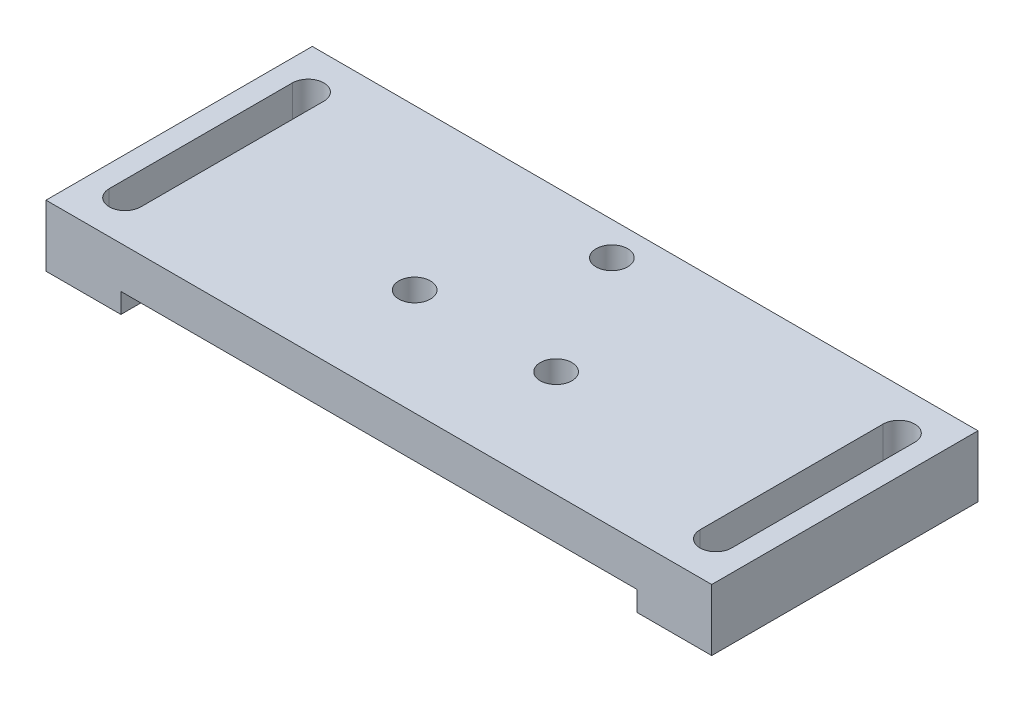
SolidWorks part; units mm, degrees
ref_plane "Front Plane" through (0, 0, 0) normal (0, 0, 1) x (1, 0, 0)
ref_plane "Top Plane" through (0, 0, 0) normal (0, 1, 0) x (1, 0, 0)
ref_plane "Right Plane" through (0, 0, 0) normal (1, 0, 0) x (0, 0, -1)
ref_axis "X-Axis" through (-88.99, 0, 0) along (1, 0, 0)
ref_axis "Y-Axis" through (0, 55, 0) along (0, -1, 0)
ref_axis "Z-Axis" through (0, 0, -88.99) along (0, 0, 1)
sketch "Sketch1" plane through (0, 0, 0) normal (0, 1, 0) x (1, 0, 0)
  line L1 (-20, -8) -> (20, -8)
  line L2 (-20, -8) -> (-20, 8)
  line L3 (-20, 8) -> (20, 8)
  line L4 (20, -8) -> (20, 8)
  line L5 (-20, -8) -> (20, 8) construction
  line L6 (-20, 8) -> (20, -8) construction
  point P0 (0, 0)
  dimension "D1" = 40
  dimension "D2" = 16
extrude "Boss-Extrude1" add sketch "Sketch1" along normal blind 2.5
sketch "Sketch2" plane through (0, 0, 0) normal (0, -1, 0) x (1, 0, 0)
  line L0 (20, -8) -> (-20, -8) construction
  line L1 (-20, 8) -> (-15.5, 8)
  line L2 (-20, 8) -> (-20, -8)
  line L3 (-20, -8) -> (-15.5, -8)
  line L4 (-15.5, 8) -> (-15.5, -8)
  dimension "D1" = 4.5
extrude "Boss-Extrude2" add sketch "Sketch2" along normal offset from surface (1.2 mm away) 3.7 up to face at (0, 2.5, 0)
sketch "Sketch3" plane through (0, -1.2, 0) normal (0, -1, 0) x (1, 0, 0)
  line L0 (-17.75, 8) -> (-17.75, -8) construction
  line L1 (-15.5, 8) -> (-20, 8) construction
  line L2 (-20, -8) -> (-15.5, -8) construction
  line L3 (-17.75, 5.5) -> (-17.75, -5.5) construction
  line L4 (-16.8, 5.5) -> (-16.8, -5.5)
  line L5 (-18.7, 5.5) -> (-18.7, -5.5)
  arc A0 (-16.8, 5.5) -> (-18.7, 5.5) centre (-17.75, 5.5) ccw
  arc A1 (-18.7, -5.5) -> (-16.8, -5.5) centre (-17.75, -5.5) ccw
  point P8 (-17.75, 0)
  dimension "D3" = 0.95
  dimension "D1" = 2.5
  dimension "D2" = 2.5
extrude "Cut-Extrude1" cut sketch "Sketch3" against normal through all
mirror "Mirror1" about plane through (0, 0, 0) normal (1, 0, 0) of "Cut-Extrude1", "Boss-Extrude2"
sketch "Sketch4" plane through (0, 2.5, 0) normal (0, 1, 0) x (1, 0, 0)
  line L0 (0, 8) -> (0, -8) construction
  line L1 (20, 8) -> (-20, 8) construction
  line L2 (-20, -8) -> (20, -8) construction
  line L3 (-4.25, -1.6) -> (4.25, -1.6) construction
  circle A0 centre (4.25, -1.6) radius 0.95
  circle A1 centre (-4.25, -1.6) radius 0.95
  circle A2 centre (0, 6) radius 0.95
  point P9 (0, -1.6)
  dimension "D2" = 1.9
  dimension "D1" = 2
  dimension "D3" = 8.5
  dimension "D4" = 7.6
extrude "Cut-Extrude2" cut sketch "Sketch4" against normal through all
equation "\"D2@Sketch3\"=\"D1@Sketch3\""
equation "\"D3@Sketch3\"=1.9/2"
